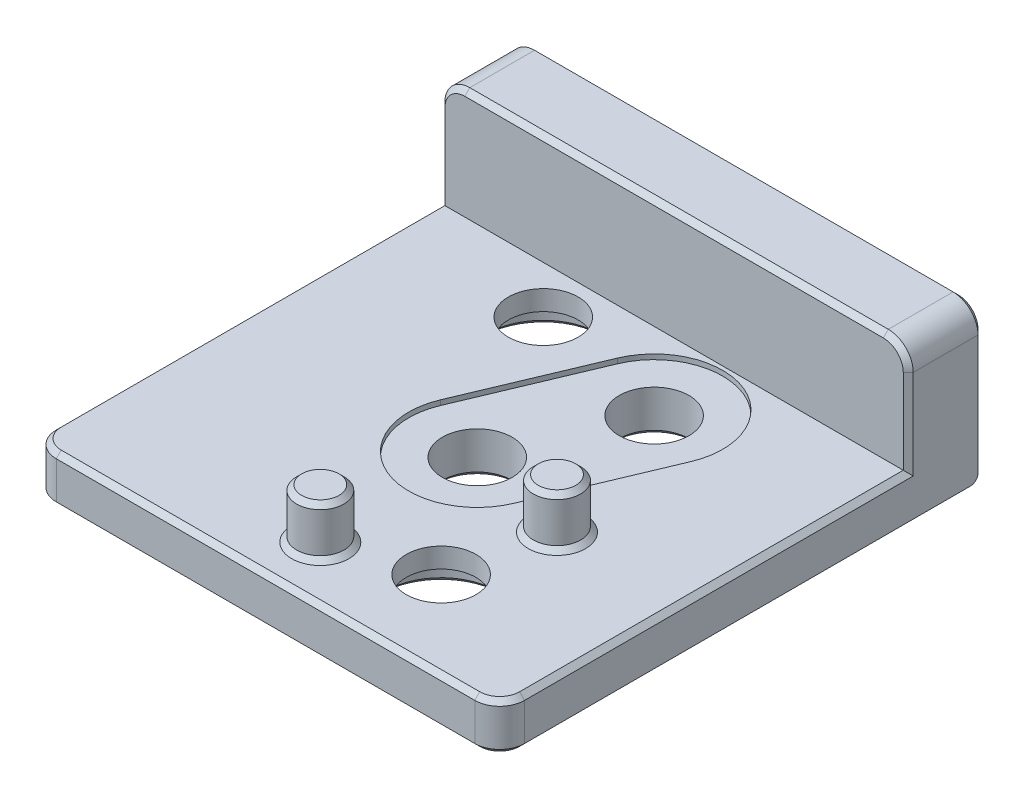
SolidWorks part; units mm, degrees
ref_plane "Front Plane" through (0, 0, 0) normal (0, 0, 1) x (1, 0, 0)
ref_plane "Top Plane" through (0, 0, 0) normal (0, 1, 0) x (1, 0, 0)
ref_plane "Right Plane" through (0, 0, 0) normal (1, 0, 0) x (0, 0, -1)
sketch "Sketch1" plane through (0, 0, 0) normal (1, 0, 0) x (0, 0, -1)
  line L1 (0, 0) -> (19.4, 0)
  line L2 (0, 0) -> (0, -1.9)
  line L3 (0, -1.9) -> (19.4, -1.9)
  line L4 (19.4, 0) -> (19.4, -1.9)
  line L5 (19.4, 0) -> (16.4, 0)
  line L6 (19.4, 0) -> (19.4, 4.4)
  line L7 (19.4, 4.4) -> (16.4, 4.4)
  line L8 (16.4, 0) -> (16.4, 4.4)
  point P8 (13.9947, 0)
  dimension "D1" = 1.9
  dimension "D2" = 3
  dimension "D3" = 16.4
  dimension "D4" = 6.3
extrude "Boss-Extrude1" add sketch "Sketch1" along normal mid plane 18.8 contours L4 L1 L2 L3 | L8 L1 L6 L7 region at (0, -0.95, -9.7) region at (0, 2.2, -17.9)
sketch "Sketch2" plane through (0, 0, 0) normal (0, 1, 0) x (1, 0, 0)
  line L0 (0, 0) -> (0, 8.5)
  line L1 (9.4, 0) -> (-9.4, 0) construction
  line L2 (9.4, 0) -> (9.4, 16.4) construction
  circle A0 centre (0, 8.5) radius 1.4
  circle A1 centre (2.1, 13.5) radius 1.4
  circle A2 centre (3.55, 3.5) radius 1.4
  circle A3 centre (-3.35, 14.5) radius 1.4
  dimension "D2" = 2.8
  dimension "D5" = 2.8
  dimension "D1" = 8.5
  dimension "D3" = 13.5
  dimension "D4" = 7.3
  dimension "D6" = 12.75
  dimension "D7" = 14.5
  dimension "D8" = 5.85
  dimension "D9" = 3.5
extrude "Cut-Extrude1" cut sketch "Sketch2" against normal through all contours A0 | A1 | A3 | A2 region at (0.9619, 0, -7.5381) region at (2.1, 0, -13.5) region at (3.55, 0, -3.5) region at (-3.35, 0, -14.5)
sketch "Sketch3" plane through (0, 0, 0) normal (0, 1, 0) x (1, 0, 0)
  line L0 (0, 8.5) -> (2.1, 13.5) construction
  line L1 (-2.5355, 9.5649) -> (-0.4355, 14.5649)
  line L2 (2.5355, 7.4351) -> (4.6355, 12.4351)
  arc A0 (-2.5355, 9.5649) -> (2.5355, 7.4351) centre (0, 8.5) ccw
  arc A1 (4.6355, 12.4351) -> (-0.4355, 14.5649) centre (2.1, 13.5) ccw
  circle A2 centre (2.1, 13.5) radius 1.4 construction
  circle A3 centre (0, 8.5) radius 1.4 construction
  point P2 (1.05, 11)
  dimension "D1" = 2.75
extrude "Cut-Extrude2" cut sketch "Sketch3" against normal blind 0.2
sketch "Sketch4" plane through (0, -1.9, 0) normal (0, -1, 0) x (1, 0, 0)
  circle A0 centre (-3.35, -14.5) radius 2.25
  circle A1 centre (3.55, -3.5) radius 2.25
  circle A2 centre (-3.35, -14.5) radius 1.4 construction
  circle A3 centre (3.55, -3.5) radius 1.4 construction
  dimension "D1" = 4.5
extrude "Cut-Extrude3" cut sketch "Sketch4" against normal blind 1.1
fillet "Fillet1" radius 1 4 edges at (-9.4, 4.4, -17.9) (9.4, 4.4, -17.9) (-9.4, -0.95, 0) (9.4, -0.95, 0)
sketch "Sketch5" plane through (0, 0, 0) normal (0, 1, 0) x (1, 0, 0)
  line L0 (9.4, 1) -> (9.4, 16.4) construction
  line L1 (8.4, 0) -> (-8.4, 0) construction
  circle A0 centre (0, 2.2) radius 0.95
  circle A1 centre (4.4, 7.3) radius 0.95
  dimension "D1" = 1.9
  dimension "D2" = 5
  dimension "D3" = 9.4
  dimension "D4" = 2.2
  dimension "D5" = 7.3
extrude "Boss-Extrude2" add sketch "Sketch5" along normal blind 2
fillet "Fillet4" radius 0.5 1 edges at (0, -1.9, -19.4)
chamfer "Chamfer1" distance 0.2 angle 45 30 edges at (9.4, 1.7, -16.4) (9.1071, 4.1071, -16.4) (0, 4.4, -16.4) (-9.4, 1.7, -16.4) (-9.1071, 4.1071, -16.4) (9.4, -1.9, -9.95) (9.4, -1.7536, -19.2536) (9.1071, -1.9, -0.2929) (9.4, 1, -19.4) (0, -1.9, 0) (9.1071, 4.1071, -19.4) (-9.1071, -1.9, -0.2929) (0, 4.4, -19.4) (-9.4, -1.9, -9.95) (-9.1071, 4.1071, -19.4) (-9.4, -1.7536, -19.2536) (-9.4, 1, -19.4) (9.4, 0, -8.7) (9.1071, 0, -0.2929) (0, 0, 0) (-9.1071, 0, -0.2929) (-9.4, 0, -8.7) (0, 0, -1.25) (0, 2, -1.25) (4.4, 0, -6.35) (4.4, 2, -6.35) (0, -1.9, -7.1) (2.1, -1.9, -12.1) (3.55, -1.9, -5.75) (-3.35, -1.9, -16.75)
